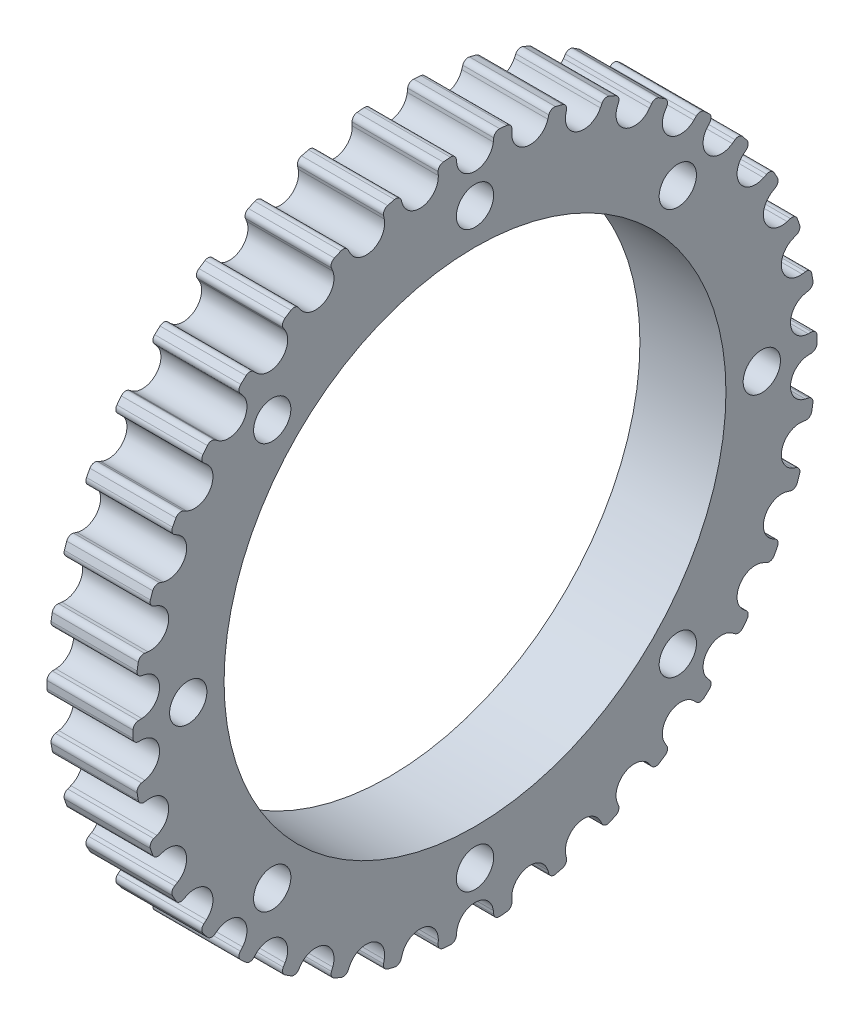
SolidWorks part; units mm, degrees
material "Thornel Mat VMA"
ref_plane "前视基准面" through (0, 0, 0) normal (0, 0, 1) x (1, 0, 0)
ref_plane "上视基准面" through (0, 0, 0) normal (0, 1, 0) x (1, 0, 0)
ref_plane "右视基准面" through (0, 0, 0) normal (1, 0, 0) x (0, 0, -1)
sketch "草图1" plane through (0, 0, 0) normal (0, 0, 1) x (1, 0, 0)
  line L0 (0, 0) -> (64.8368, 0) construction
  line L1 (0, 0) -> (0, 47.699)
  line L2 (0, 47.699) -> (28, 47.699)
  line L3 (28, 47.699) -> (28, 22.1356)
  line L4 (28, 22.1356) -> (20, 22.1356)
  line L5 (20, 22.1356) -> (20, 0)
  line L6 (20, 0) -> (0, 0)
  dimension "L" = 20
  dimension "B" = 28
  dimension "d1" = 44.2712
  dimension "da" = 95.398
revolve "旋转1" add sketch "草图1" angle 360 about L0
ref_axis "基准轴1" through (-1.4, 0, 0) along (1, 0, 0)
sketch "草图6" plane through (0, 0, 0) normal (1, 0, 0) x (0, 0, -1)
  line L0 (0, 0) -> (0, 30.6512) construction
  line L1 (2.6093, 46.8919) -> (2.5508, 46.4158)
  line L2 (4.2172, 47.5122) -> (4.4139, 49.1138)
  line L3 (-4.2172, 47.5122) -> (-4.4139, 49.1138)
  line L4 (-2.6093, 46.8919) -> (-2.5508, 46.4158)
  circle A0 centre (0, 0) radius 47.699 construction
  circle A1 centre (0, 0) radius 44.159 construction
  arc A2 (-2.5508, 46.4158) -> (2.5508, 46.4158) centre (0, 46.729) ccw
  arc A3 (4.4139, 49.1138) -> (-4.4139, 49.1138) centre (0, 0) ccw
  arc A4 (2.6093, 46.8919) -> (3.4397, 47.5748) centre (3.3835, 46.7968) cw
  arc A5 (3.4397, 47.5748) -> (4.2172, 47.5122) centre (0, 0) cw
  arc A6 (-3.4397, 47.5748) -> (-4.2172, 47.5122) centre (0, 0) ccw
  arc A7 (-2.6093, 46.8919) -> (-3.4397, 47.5748) centre (-3.3835, 46.7968) ccw
  point P7 (0, 5.35)
  point P8 (0, 27.1112)
  point P15 (2.699, 47.6226)
  dimension "D1" = 88.318
  dimension "ra" = 0.78
  dimension "rf" = 2.57
  dimension "hg" = 3.54
  dimension "D3" = 0.78
  dimension "D4" = 1.6136
  dimension "angle" = 14
  dimension "bw" = 5.35
extrude "切除-拉伸2" cut sketch "草图6" along normal up to next
pattern_circular "阵列(圆周)3" count 38 over 360 about axis through (-1.4, 0, 0) along (1, 0, 0) of "切除-拉伸2"
sketch "草图8" plane through (28, 0, 0) normal (1, 0, 0) x (0, 0, -1)
  circle A0 centre (0, 0) radius 49
  dimension "D1" = 98
extrude "切除-拉伸4" cut sketch "草图8" against normal offset from surface (16 mm away) 12 up to face at (0, 0, 0)
sketch "草图9" plane through (12, 0, 0) normal (1, 0, 0) x (0, 0, -1)
  circle A0 centre (0, 0) radius 35
  circle A1 centre (0, 0) radius 40 construction
  circle A2 centre (0, 40) radius 2.6
  circle A3 centre (28.2843, 28.2843) radius 2.6
  circle A4 centre (40, 0) radius 2.6
  circle A5 centre (28.2843, -28.2843) radius 2.6
  circle A6 centre (0, -40) radius 2.6
  circle A7 centre (-28.2843, -28.2843) radius 2.6
  circle A8 centre (-40, 0) radius 2.6
  circle A9 centre (-28.2843, 28.2843) radius 2.6
  point P23 (0, 0)
  dimension "D1" = 70
  dimension "D2" = 80
  dimension "D3" = 5.2
  dimension "D4" = 8
extrude "切除-拉伸5" cut sketch "草图9" against normal blind 20
equation "\"D1@草图6\" = \"da@草图1\"  - \"hg@草图6\" - \"hg@草图6\""
equation "\"D3@草图6\" = \"ra@草图6\""
